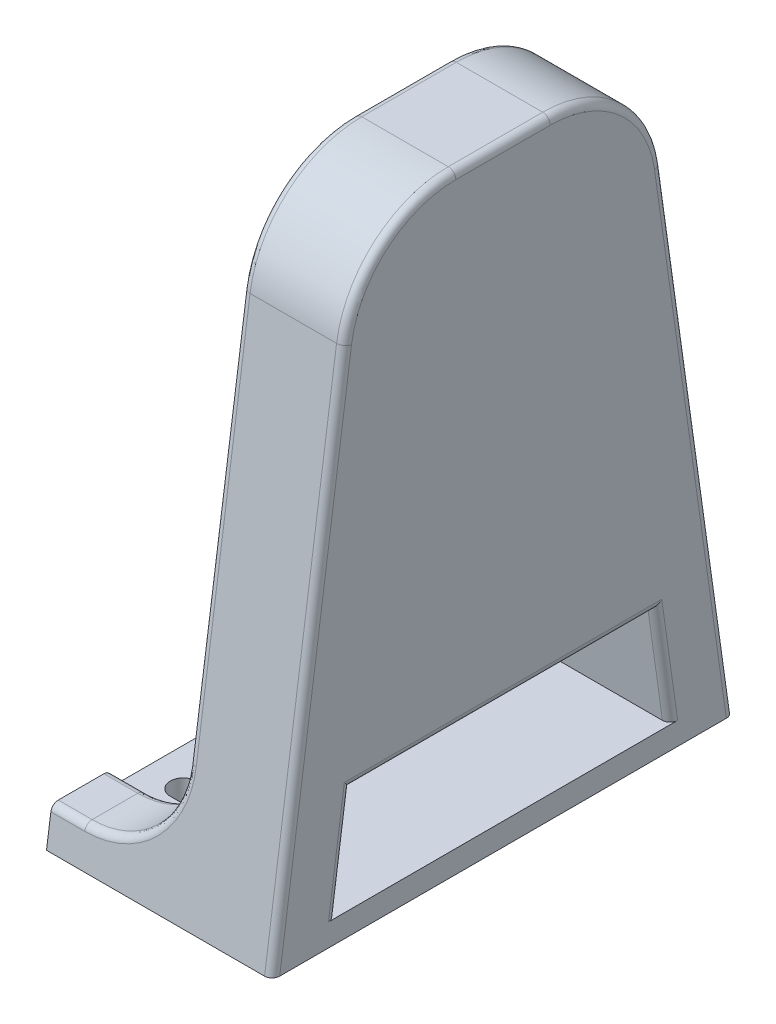
SolidWorks part; units mm, degrees
ref_plane "정면" through (0, 0, 0) normal (0, 0, 1) x (1, 0, 0)
ref_plane "윗면" through (0, 0, 0) normal (0, 1, 0) x (1, 0, 0)
ref_plane "우측면" through (0, 0, 0) normal (1, 0, 0) x (0, 0, -1)
sketch "스케치1" plane through (0, 0, 0) normal (0, 1, 0) x (1, 0, 0)
  line L1 (-15, 30) -> (15, 30)
  line L2 (-15, 30) -> (-15, -30)
  line L3 (-15, -30) -> (15, -30)
  line L4 (15, 30) -> (15, -30)
  line L5 (-15, 30) -> (15, -30) construction
  line L6 (-15, -30) -> (15, 30) construction
  point P0 (0, 0)
  dimension "D1" = 30
  dimension "D2" = 60
extrude "보스-돌출1" add sketch "스케치1" along normal blind 5
sketch "스케치2" plane through (0, 5, 0) normal (0, 1, 0) x (1, 0, 0)
  line L0 (-15, -30) -> (15, -30) construction
  line L1 (1.5, 30) -> (15, 30)
  line L2 (1.5, 30) -> (1.5, -30)
  line L3 (1.5, -30) -> (15, -30)
  line L4 (15, 30) -> (15, -30)
  line L5 (15, -30) -> (15, 30) construction
  dimension "D1" = 13.5
extrude "보스-돌출2" add sketch "스케치2" along normal blind 76
draft "구배1" type of draft neutral plane draft angle 8 faces to draft 2 face at (0.5, 28.6667, -30) face at (0.5, 28.6667, 30) neutral plane through (0, 5, 0) neutral plane normal (0, 1, 0) parameters "D1"=8
fillet "필렛1" radius 15 2 edges at (8.25, 81, 19.3189) (8.25, 81, -19.3189)
sketch "스케치3" plane through (1.5, 0, 0) normal (-1, 0, 0) x (0, 0, 1)
  line L0 (0, 81) -> (0, 0) construction
  line L1 (-6.2796, 81) -> (6.2796, 81) construction
  line L2 (-30.7027, 0) -> (30.7027, 0) construction
  circle A0 centre (0, 59.9) radius 18.5
  dimension "D1" = 37
  dimension "D2" = 59.9
extrude "컷-돌출1" cut sketch "스케치3" against normal blind 9.05
sketch "스케치4" plane through (10.55, 0, 0) normal (-1, 0, 0) x (0, 0, 1)
  circle A0 centre (0, 59.9) radius 16.5
  circle A1 centre (0, 59.9) radius 18.5 construction
  dimension "D1" = 2
extrude "컷-돌출2" cut sketch "스케치4" against normal blind 0.5
sketch "스케치5" plane through (11.05, 0, 0) normal (-1, 0, 0) x (0, 0, 1)
  circle A0 centre (0, 59.9) radius 9.75
  dimension "D1" = 19.5
extrude "보스-돌출3" add sketch "스케치5" along normal blind 2
sketch "스케치6" plane through (0, 5, 0) normal (0, 1, 0) x (1, 0, 0)
  line L0 (-15, 0) -> (15, 0) construction
  line L1 (-10, 17.5) -> (-4, 17.5) construction
  line L2 (-10, 17.5) -> (-10, -17.5) construction
  line L3 (-10, -17.5) -> (-4, -17.5) construction
  line L4 (-4, 17.5) -> (-4, -17.5) construction
  line L7 (-15, 30) -> (-15, -30) construction
  line L8 (15, -6.2796) -> (15, 6.2796) construction
  line L9 (-10, 17.5) -> (-4, 17.5) construction
  line L10 (-10, 19.25) -> (-4, 19.25)
  line L11 (-10, 15.75) -> (-4, 15.75)
  line L12 (-10, -17.5) -> (-4, -17.5) construction
  line L13 (-10, -15.75) -> (-4, -15.75)
  line L14 (-10, -19.25) -> (-4, -19.25)
  arc A0 (-10, 19.25) -> (-10, 15.75) centre (-10, 17.5) ccw
  arc A1 (-4, 15.75) -> (-4, 19.25) centre (-4, 17.5) ccw
  arc A2 (-10, -15.75) -> (-10, -19.25) centre (-10, -17.5) ccw
  arc A3 (-4, -19.25) -> (-4, -15.75) centre (-4, -17.5) ccw
  point P11 (-7, 17.5)
  point P16 (-7, -17.5)
  dimension "D4" = 1.75
  dimension "D1" = 6
  dimension "D2" = 17.5
  dimension "D3" = 5
  dimension "D5" = 35
extrude "컷-돌출3" cut sketch "스케치6" against normal through all
sketch "스케치7" plane through (15, 0, 0) normal (1, 0, 0) x (0, 0, -1)
  line L0 (-30.7027, 0) -> (30.7027, 0) construction
  line L1 (-21.1336, 68.0876) -> (-30.7027, 0) construction
  line L2 (21.1336, 68.0876) -> (30.7027, 0) construction
  line L6 (-20.2349, 17) -> (-22.2025, 3)
  line L8 (22.2025, 3) -> (20.2349, 17)
  line L10 (-20.2349, 17) -> (20.2349, 17)
  line L17 (-22.2025, 3) -> (22.2025, 3)
  dimension "D3" = 8
  dimension "D1" = 3
  dimension "D2" = 8
  dimension "D4" = 14
extrude "컷-돌출4" cut sketch "스케치7" against normal through all
fillet "필렛4" radius 12 2 edges at (1.5, 5, 25.9607) (1.5, 5, -25.9607)
fillet "필렛5" radius 1 22 edges at (-12.75, 5, -21.9214) (-2.0147, 8.5147, -21.4274) (-12.75, 5, 21.9214) (-2.0147, 8.5147, 21.4274) (15, 34.0438, 25.9182) (15, 77.3206, 16.1205) (15, 34.0438, -25.9182) (15, 77.3206, -16.1205) (-12.75, 5, -30) (-2.0147, 8.5147, -29.506) (1.5, 42.5438, -24.7236) (1.5, 77.3206, -16.1205) (-12.75, 5, 30) (-2.0147, 8.5147, 29.506) (1.5, 42.5438, 24.7236) (1.5, 77.3206, 16.1205) (15, 10, -21.2187) (15, 10, 21.2187) (15, 17, 0) (1.5, 17, 0) (15, 81, 0) (1.5, 81, 0)
chamfer "모따기1" distance 0.2 angle 45 1 edges at (1.5, 59.9, 18.5)
